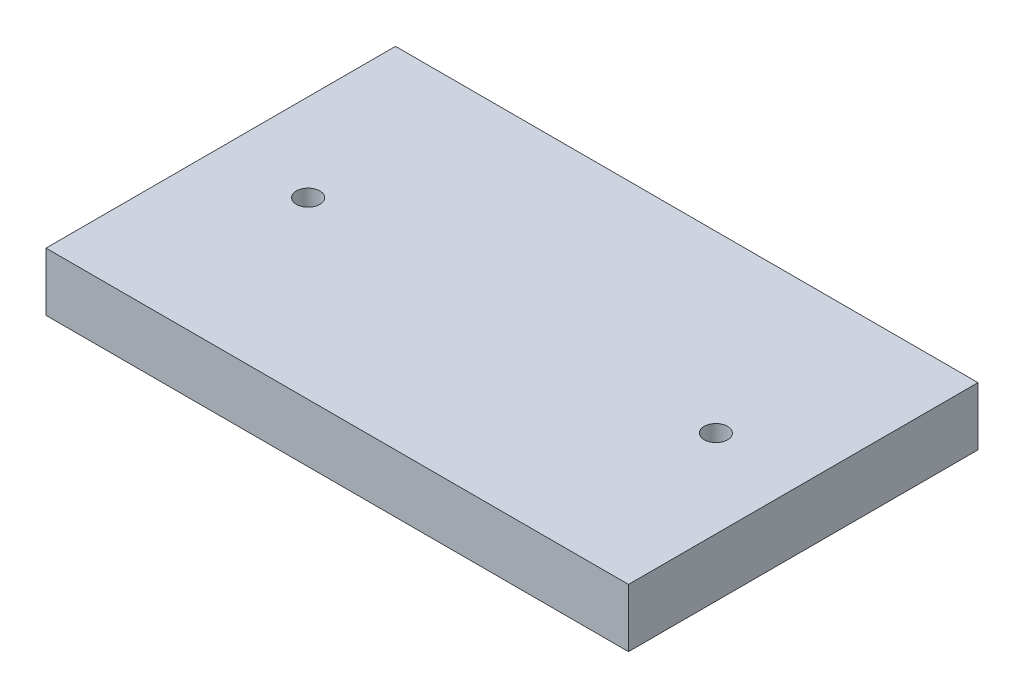
SolidWorks part; units mm, degrees
material "3003 Alloy"
ref_plane "Front Plane" through (0, 0, 0) normal (0, 0, 1) x (1, 0, 0)
ref_plane "Top Plane" through (0, 0, 0) normal (0, 1, 0) x (1, 0, 0)
ref_plane "Right Plane" through (0, 0, 0) normal (1, 0, 0) x (0, 0, -1)
sketch "Sketch1" plane through (0, 0, 0) normal (0, 1, 0) x (1, 0, 0)
  line L1 (0, 0) -> (127, 0)
  line L2 (0, 0) -> (0, 76.2)
  line L3 (0, 76.2) -> (127, 76.2)
  line L4 (127, 0) -> (127, 76.2)
  dimension "D1" = 127
  dimension "D2" = 76.2
extrude "Boss-Extrude1" add sketch "Sketch1" along normal blind 12.7
hole_wizard "CBORE for #10 Socket Head Cap Screw1" positions "Sketch5" profile "Sketch6" counterbore size "#10" standard "ANSI Inch" end condition up to next
sketch "Sketch5" plane through (0, 0, 0) normal (0, -1, 0) x (-1, 0, 0)
  line L0 (0, 0) -> (-127, 0) construction
  line L1 (-127, 0) -> (-127, 76.2) construction
  point P0 (-19.05, 38.1)
  point P2 (-107.95, 38.1)
  dimension "D1" = 38.1
  dimension "D2" = 38.1
  dimension "D3" = 19.05
  dimension "D4" = 88.9
sketch "Sketch6" plane through (19.05, 0, -38.1) normal (1, 0, 0) x (0, 0, -1)
  line L0 (0, 0) -> (0, 12.7)
  line L1 (0, 12.7) -> (2.5527, 12.7)
  line L3 (2.5527, 12.7) -> (2.5527, 4.826)
  line L4 (2.5527, 4.826) -> (4.7625, 4.826)
  line L5 (4.7625, 4.826) -> (4.7625, 0)
  line L7 (4.7625, 0) -> (0, 0)
  line L11 (0, -6.35) -> (0, 107.95) construction
  dimension "Thru Hole Dia." = 5.1054
  dimension "Thru Hole Depth" = 12.7
  dimension "C'Bore Dia." = 9.525
  dimension "C'Bore Depth" = 4.826
